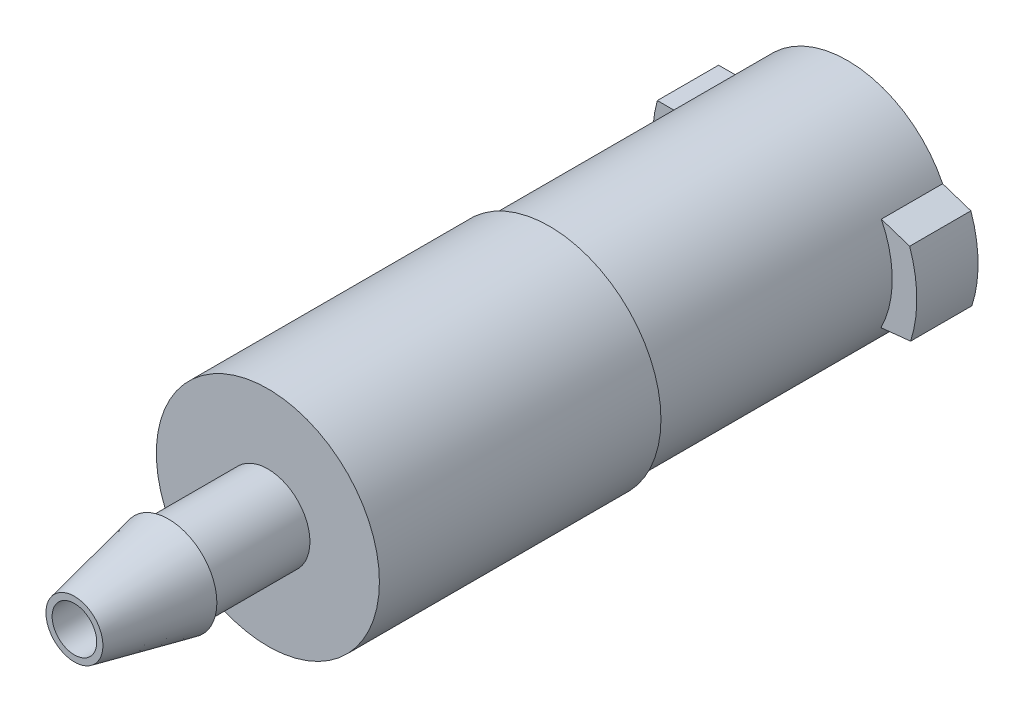
SolidWorks part; units mm, degrees
material "PVC Rigid"
ref_plane "Front Plane" through (0, 0, 0) normal (0, 0, 1) x (1, 0, 0)
ref_plane "Top Plane" through (0, 0, 0) normal (0, 1, 0) x (1, 0, 0)
ref_plane "Right Plane" through (0, 0, 0) normal (1, 0, 0) x (0, 0, -1)
sketch "Sketch1" plane through (0, 0, 0) normal (0, 0, 1) x (1, 0, 0)
  line L0 (2.8717, 1.4119) -> (3.7251, 1.1306)
  line L1 (2.8613, -1.4328) -> (3.755, -1.338)
  line L2 (-2.9936, 1.1306) -> (-3.8922, 1.1306)
  line L3 (-3.7561, -1.3501) -> (-2.8613, -1.4328)
  circle A0 centre (0, 0) radius 2.145
  circle A1 centre (0, 0) radius 3.2
  arc A2 (3.7251, 1.1306) -> (3.755, -1.338) centre (0.0514, -0.1483) cw
  arc A3 (-3.8922, 1.1306) -> (-3.7561, -1.3501) centre (-0.1434, 0.0922) ccw
  dimension "D1" = 4.29
  dimension "D2" = 3.89
  dimension "D3" = 3.89
ref_plane "Plane1" through (0, 0, 9) normal (0, 0, 1) x (1, 0, 0)
sketch "Sketch2" plane through (0, 0, 9) normal (0, 0, 1) x (1, 0, 0)
  circle A0 centre (0, 0) radius 3.3674
  circle A1 centre (0, 0) radius 1.27
  dimension "D1" = 2.54
extrude "Boss-Extrude1" add sketch "Sketch1" along normal blind 9 contours A1
extrude "Cut-Extrude7" cut sketch "Sketch1<371>" along normal blind 9 contours A0 region at (0, 0, 0)
sketch "Sketch1<371>" plane through (0, 0, 0) normal (0, 0, 1) x (1, 0, 0) same geometry as "Sketch1"
extrude "Boss-Extrude3" add sketch "Sketch2" along normal blind 8.5
extrude "Boss-Extrude4" add sketch "Sketch1<372>" along normal blind 1.85 contours L2 A3 L3 A1 | A2 L0 A1 L1 region at (3.4729, -0.0901, 0) region at (-3.5318, -0.1202, 0)
sketch "Sketch1<372>" plane through (0, 0, 0) normal (0, 0, 1) x (1, 0, 0) same geometry as "Sketch1"
ref_plane "Plane2" through (0, 0, 17.5) normal (0, 0, 1) x (1, 0, 0)
sketch "Sketch7" plane through (0, 0, 17.5) normal (0, 0, 1) x (1, 0, 0)
  circle A0 centre (0, 0) radius 1.27
  circle A1 centre (0, 0) radius 1
extrude "Boss-Extrude5" add sketch "Sketch7" along normal blind 3 separate body
ref_plane "Plane3" through (0, 0, 20.5) normal (0, 0, 1) x (1, 0, 0)
sketch "Sketch9" plane through (0, 0, 20.5) normal (0, 0, 1) x (1, 0, 0)
  circle A0 centre (0, 0) radius 1.46
ref_plane "Plane4" through (0, 0, 23.34) normal (0, 0, 1) x (1, 0, 0)
sketch "Sketch10" plane through (0, 0, 23.34) normal (0, 0, 1) x (1, 0, 0)
  circle A0 centre (0, 0) radius 0.86
loft "Loft1" add profiles "Sketch9", "Sketch10" connector at (1.0958, 0.9648, 20.5) connector at (0.6602, 0.5511, 23.34)
sketch "Sketch11" plane through (0, 0, 23.34) normal (0, 0, 1) x (1, 0, 0)
  circle A0 centre (0, 0) radius 0.6735
extrude "Cut-Extrude8" cut sketch "Sketch11" against normal blind 10
